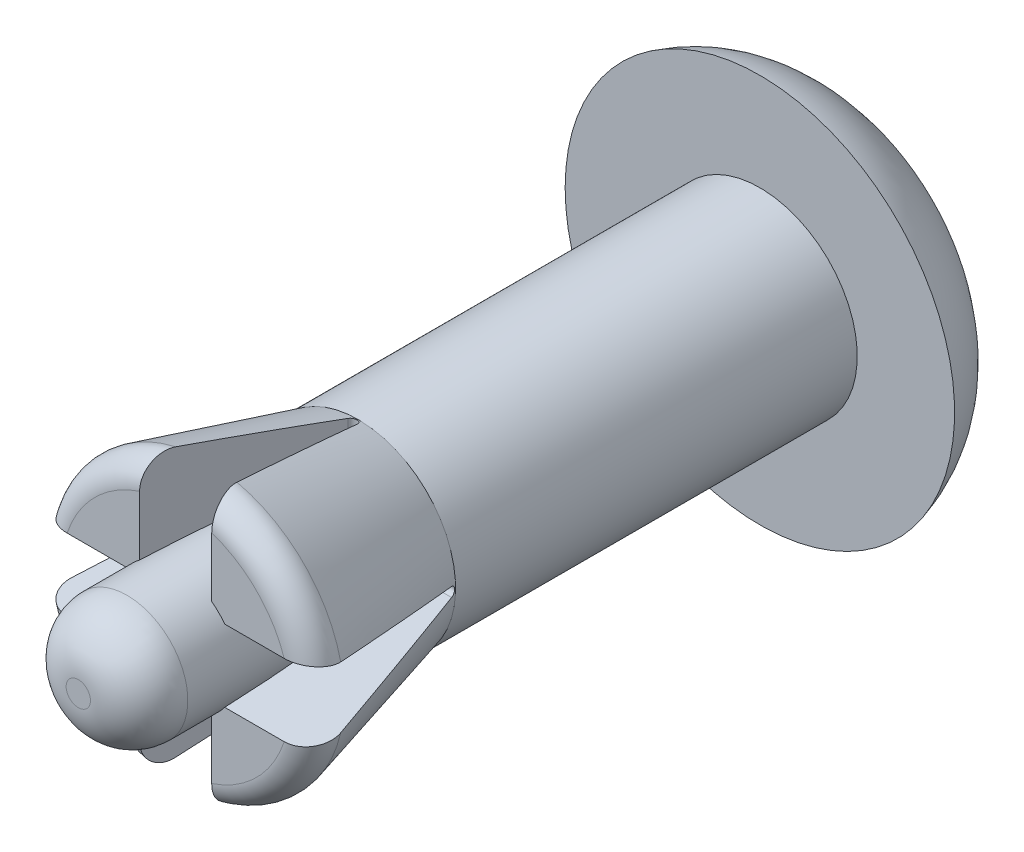
SolidWorks part; units mm, degrees
material "PE Low/Medium Density"
ref_plane "Front Plane" through (0, 0, 0) normal (0, 0, 1) x (1, 0, 0)
ref_plane "Top Plane" through (0, 0, 0) normal (0, 1, 0) x (1, 0, 0)
ref_plane "Right Plane" through (0, 0, 0) normal (1, 0, 0) x (0, 0, -1)
sketch "Sketch1" plane through (0, 0, 0) normal (0, 1, 0) x (1, 0, 0)
  line L0 (0, -14) -> (0, 2)
  line L1 (0, 5.0635) -> (0, -10.819) construction
  line L2 (2, 0) -> (4, 0)
  line L3 (2, 0) -> (2, -8.25)
  line L4 (2, -8.25) -> (3, -12)
  line L5 (3, -12) -> (1.25, -12)
  line L6 (1.25, -12) -> (1.25, -14)
  line L7 (1.25, -14) -> (0, -14)
  arc A0 (0, 2) -> (1.9975, 1.8326) centre (0, -10) cw
  arc A1 (1.9975, 1.8326) -> (4, 0) centre (1.5813, -0.6325) cw
  dimension "D5" = 12
  dimension "D6" = 2.5
  dimension "D1" = 2
  dimension "D2" = 16
  dimension "D3" = 8
  dimension "D4" = 4
  dimension "D7" = 14
  dimension "D8" = 8.25
  dimension "D9" = 6
  dimension "D10" = 2.5
revolve "Revolve1" add sketch "Sketch1" angle 360 about L1
fillet "Fillet1" radius 1 1 edges at (-1.25, 0, 14)
fillet "Fillet2" radius 0.5 1 edges at (-3, 0, 12)
ref_plane "Plane1" through (0, 4, 0) normal (0, 1, 0) x (1, 0, 0)
sketch "Sketch2" plane through (0, 4, 0) normal (0, 1, 0) x (1, 0, 0)
  line L0 (0, 4.7066) -> (0, -12.7867) construction
  line L1 (0, -7.8) -> (0.7406, -12)
  line L2 (0.7406, -12) -> (-0.7406, -12)
  line L3 (0, -7.8) -> (-0.7406, -12)
  line L4 (-2.3492, -12) -> (2.3492, -12) construction
  line L5 (-2, 0) -> (2, 0) construction
  point P7 (0, -12)
  dimension "D1" = 20
  dimension "D2" = 7.8
extrude "Cut-Extrude1" cut sketch "Sketch2" against normal up to surface (2.993 mm away) up to face at (-1.25, 0, 13)
fillet "Fillet3" radius 0.1 1 edges at (0, 1.625, 7.8)
pattern_circular "CirPattern1" count 4 over 360 of "Cut-Extrude1", "Fillet3"
